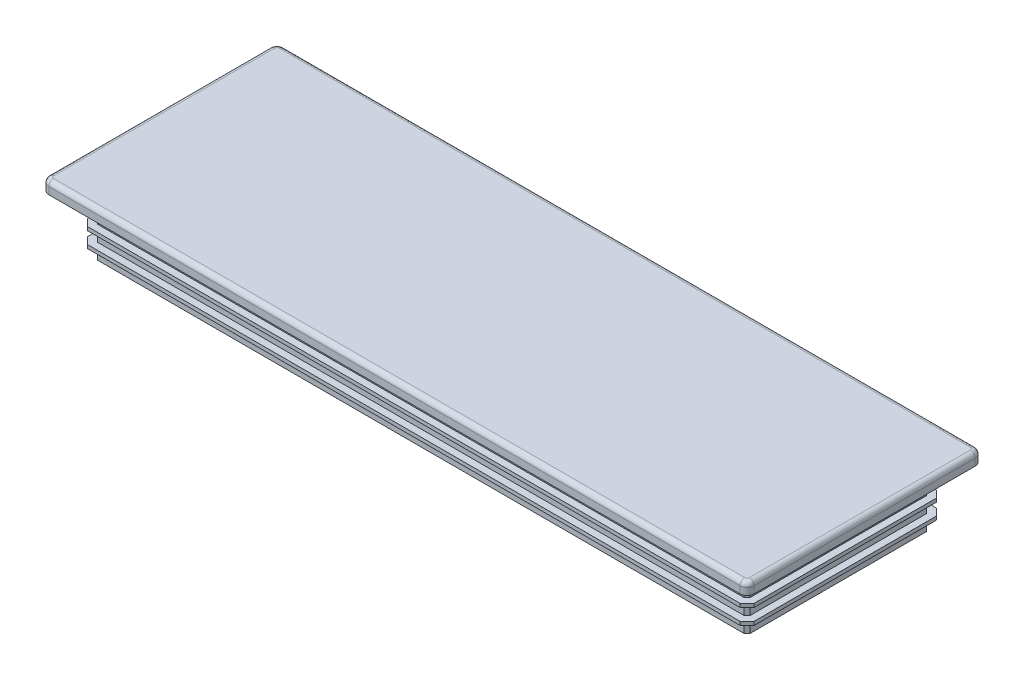
SolidWorks part; units mm, degrees
material "ABS"
ref_plane "Front" through (0, 0, 0) normal (0, 0, 1) x (1, 0, 0)
ref_plane "Top" through (0, 0, 0) normal (0, 1, 0) x (1, 0, 0)
ref_plane "Right" through (0, 0, 0) normal (1, 0, 0) x (0, 0, -1)
sketch "Sketch5" plane through (0, 0, 0) normal (0, 0, 1) x (1, 0, 0)
  line L0 (0, 0) -> (0, 12.7) construction
  dimension "Height" = 12.7
sketch "Sketch1" plane through (0, 0, 0) normal (0, 1, 0) x (1, 0, 0)
  line L1 (-72.009, 21.209) -> (72.009, 21.209)
  line L2 (-72.009, 21.209) -> (-72.009, -21.209)
  line L3 (-72.009, -21.209) -> (72.009, -21.209)
  line L4 (72.009, 21.209) -> (72.009, -21.209)
  line L5 (-72.009, 21.209) -> (72.009, -21.209) construction
  line L6 (-72.009, -21.209) -> (72.009, 21.209) construction
  line L21 (76.2, 25.4) -> (-76.2, 25.4) construction
  line L22 (76.2, 25.4) -> (76.2, -25.4) construction
  line L23 (76.2, -25.4) -> (-76.2, -25.4) construction
  line L24 (-76.2, 25.4) -> (-76.2, -25.4) construction
  line L25 (76.2, 25.4) -> (-76.2, -25.4) construction
  line L26 (76.2, -25.4) -> (-76.2, 25.4) construction
  point P0 (0, 0)
  point P6 (0, 0)
  point P11 (0, 0)
  point P22 (0, 0)
  dimension "D1" = 4.191
  dimension "Head Length" = 152.4
  dimension "Head Width" = 50.8
  dimension "D2" = 4.191
extrude "Boss-Extrude1" add sketch "Sketch1" along normal up to vertex (12.7 mm away) up to point (0, 12.7, 0)
sketch "Sketch2" plane through (0, 12.7, 0) normal (0, 1, 0) x (1, 0, 0)
  line L0 (-76.2, 25.4) -> (-76.2, -25.4) construction
  line L1 (76.2, 25.4) -> (-76.2, 25.4) construction
  line L2 (76.2, 25.4) -> (76.2, -25.4) construction
  line L3 (76.2, -25.4) -> (-76.2, -25.4) construction
  line L4 (-76.2, 23.876) -> (-76.2, -23.876)
  line L5 (74.676, 25.4) -> (-74.676, 25.4)
  line L6 (76.2, 23.876) -> (76.2, -23.876)
  line L7 (74.676, -25.4) -> (-74.676, -25.4)
  arc A0 (-76.2, -23.876) -> (-74.676, -25.4) centre (-74.676, -23.876) ccw
  arc A1 (76.2, -23.876) -> (74.676, -25.4) centre (74.676, -23.876) cw
  arc A2 (74.676, 25.4) -> (76.2, 23.876) centre (74.676, 23.876) cw
  arc A3 (-76.2, 23.876) -> (-74.676, 25.4) centre (-74.676, 23.876) cw
  dimension "D1" = 1.524
extrude "Boss-Extrude2" add sketch "Sketch2" along normal blind 2.54
chamfer "Chamfer1" distance 1.524 angle 45 4 edges at (72.009, 6.35, -21.209) (72.009, 6.35, 21.209) (-72.009, 6.35, -21.209) (-72.009, 6.35, 21.209)
shell "Shell1" thickness 2.54 removed face at (0, 0, 0)
sketch "Sketch3" plane through (0, 0, 0) normal (0, -1, 0) x (-1, 0, 0)
  line L4 (-72.009, 19.685) -> (-72.009, -19.685)
  line L5 (-72.009, 19.685) -> (-72.009, -19.685)
  line L6 (-70.485, -21.209) -> (70.485, -21.209)
  line L7 (-70.485, -21.209) -> (70.485, -21.209)
  line L8 (72.009, -19.685) -> (72.009, 19.685)
  line L9 (72.009, -19.685) -> (72.009, 19.685)
  line L10 (70.485, 21.209) -> (-70.485, 21.209)
  line L11 (70.485, 21.209) -> (-70.485, 21.209)
  line L16 (-70.485, 21.209) -> (-72.009, 19.685)
  line L17 (-70.485, 21.209) -> (-72.009, 19.685)
  line L18 (-72.009, -19.685) -> (-70.485, -21.209)
  line L19 (-72.009, -19.685) -> (-70.485, -21.209)
  line L20 (70.485, -21.209) -> (72.009, -19.685)
  line L21 (70.485, -21.209) -> (72.009, -19.685)
  line L22 (72.009, 19.685) -> (70.485, 21.209)
  line L23 (72.009, 19.685) -> (70.485, 21.209)
  dimension "D1" = 0
sketch "Sketch4" plane through (0, 0, 0) normal (0, 0, 1) x (1, 0, 0)
  line L1 (72.009, 2.6035) -> (70.485, 2.6035)
  line L2 (72.009, 2.6035) -> (72.009, 0)
  line L3 (72.009, 0) -> (70.485, 0)
  line L4 (70.485, 2.6035) -> (70.485, 0)
  line L5 (76.2, 0) -> (-76.2, 0) construction
  line L6 (-74.676, 12.7) -> (74.676, 12.7) construction
  line L7 (72.009, 9.3345) -> (70.485, 9.3345)
  line L8 (72.009, 9.3345) -> (72.009, 6.731)
  line L9 (72.009, 6.731) -> (70.485, 6.731)
  line L10 (70.485, 9.3345) -> (70.485, 6.731)
  line L11 (72.009, 10.0965) -> (70.485, 10.0965)
  line L12 (72.009, 10.0965) -> (72.009, 12.7)
  line L13 (72.009, 12.7) -> (70.485, 12.7)
  line L14 (70.485, 10.0965) -> (70.485, 12.7)
  line L15 (72.009, 10.0965) -> (72.009, 9.3345) construction
  line L16 (70.485, 5.969) -> (72.009, 5.969)
  line L17 (70.485, 5.969) -> (70.485, 3.3655)
  line L18 (70.485, 3.3655) -> (72.009, 3.3655)
  line L19 (72.009, 5.969) -> (72.009, 3.3655)
  line L20 (72.009, 6.731) -> (72.009, 5.969) construction
  line L21 (72.009, 3.3655) -> (72.009, 2.6035) construction
  line L22 (72.009, 12.7) -> (72.009, 0) construction
  line L23 (74.676, 12.7) -> (76.2, 12.7) construction
  line L26 (70.485, 0) -> (70.485, 12.7) construction
  dimension "D1" = 0.762
sweep "Cut-Sweep2" cut profiles "Sketch4" path "Sketch3"
fillet "Fillet2" radius 1.016 8 edges at (-76.2, 15.24, 0) (-75.7536, 15.24, -24.9536) (0, 15.24, -25.4) (75.7536, 15.24, -24.9536) (76.2, 15.24, 0) (75.7536, 15.24, 24.9536) (0, 15.24, 25.4) (-75.7536, 15.24, 24.9536)
